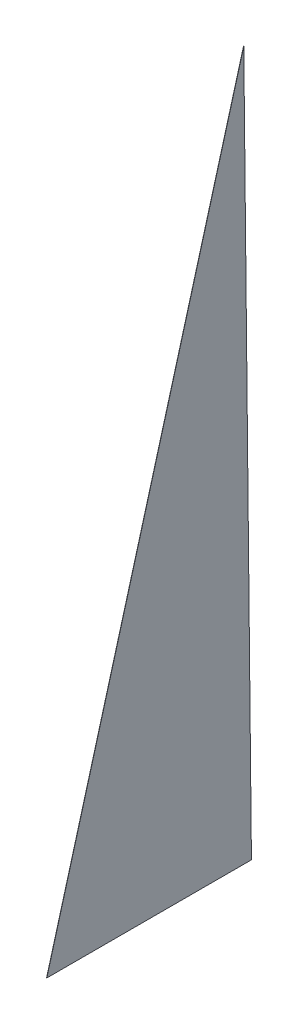
SolidWorks part; units mm, degrees
material "Corrugated Paper"
ref_plane "Front Plane" through (0, 0, 0) normal (0, 0, 1) x (1, 0, 0)
ref_plane "Top Plane" through (0, 0, 0) normal (0, 1, 0) x (1, 0, 0)
ref_plane "Right Plane" through (0, 0, 0) normal (1, 0, 0) x (0, 0, -1)
sketch "Sketch1" plane through (0, 0, 0) normal (1, 0, 0) x (0, 0, -1)
  line L0 (0, 0) -> (168.45, 605.88)
  line L1 (168.45, 605.88) -> (175, 0)
  line L2 (175, 0) -> (0, 0)
  dimension "D1" = 175
  dimension "D2" = 605.88
  dimension "D3" = 168.45
extrude "Boss-Extrude1" add sketch "Sketch1" along normal blind 0.1984
